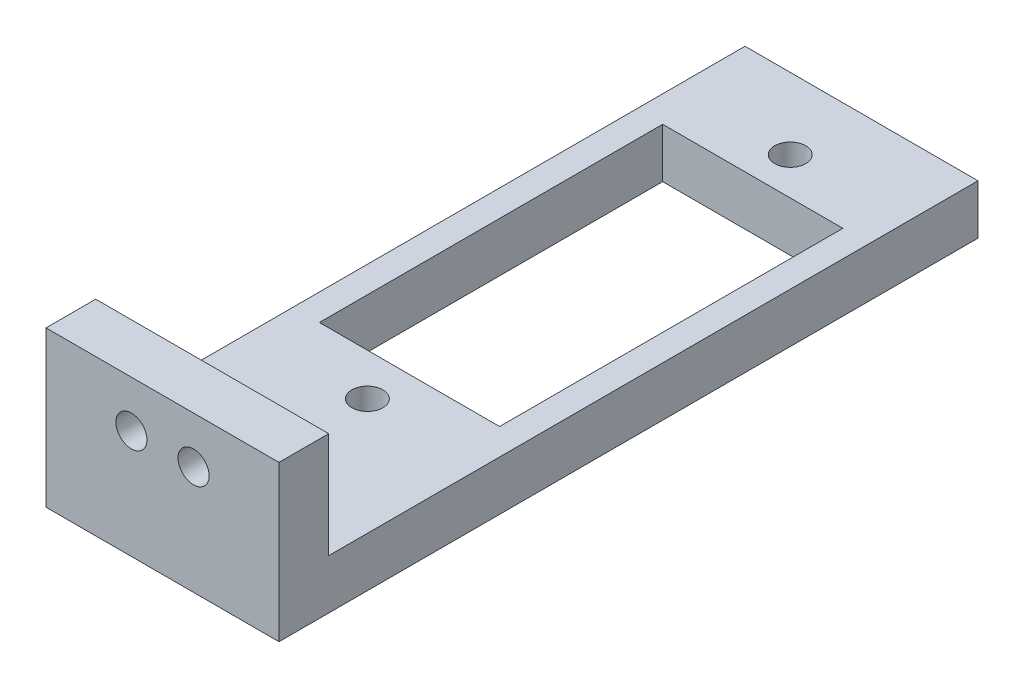
SolidWorks part; units mm, degrees
ref_plane "Front Plane" through (0, 0, 0) normal (0, 0, 1) x (1, 0, 0)
ref_plane "Top Plane" through (0, 0, 0) normal (0, 1, 0) x (1, 0, 0)
ref_plane "Right Plane" through (0, 0, 0) normal (1, 0, 0) x (0, 0, -1)
sketch "Sketch1" plane through (0, 0, 0) normal (0, 1, 0) x (1, 0, 0)
  line L1 (-7.5, 22.5) -> (7.5, 22.5)
  line L2 (-7.5, 22.5) -> (-7.5, -22.5)
  line L3 (-7.5, -22.5) -> (7.5, -22.5)
  line L4 (7.5, 22.5) -> (7.5, -22.5)
  line L5 (-7.5, 22.5) -> (7.5, -22.5) construction
  line L6 (-7.5, -22.5) -> (7.5, 22.5) construction
  point P0 (0, 0)
  dimension "D1" = 15
  dimension "D2" = 45
extrude "Boss-Extrude1" add sketch "Sketch1" along normal blind 10
sketch "Sketch4" plane through (0, 0, -22.5) normal (0, 0, -1) x (-1, 0, 0)
  line L0 (-7.5, 10) -> (-7.5, 0) construction
  line L1 (-7.5, 3.2) -> (7.5, 3.2)
  line L2 (-7.5, 3.2) -> (-7.5, 10)
  line L3 (-7.5, 10) -> (7.5, 10)
  line L4 (7.5, 3.2) -> (7.5, 10)
  dimension "D1" = 6.8
extrude "Cut-Extrude2" cut sketch "Sketch4" against normal blind 41.8
sketch "Sketch5" plane through (0, 0, 22.5) normal (0, 0, 1) x (1, 0, 0)
  line L1 (-7.5, 10) -> (7.5, 10) construction
  line L3 (-7.5, 10) -> (-7.5, 0) construction
  circle A0 centre (-2, 7) radius 1
  circle A1 centre (2, 7) radius 1
  dimension "D1" = 2
  dimension "D2" = 2
  dimension "D3" = 3
  dimension "D4" = 0
  dimension "D5" = 4
  dimension "D6" = 5.5
extrude "Cut-Extrude3" cut sketch "Sketch5" against normal through all
sketch "Sketch6" plane through (0, 3.2, 0) normal (0, 1, 0) x (1, 0, 0)
  line L1 (5.8, 15.5) -> (-5.8, 15.5)
  line L2 (5.8, 15.5) -> (5.8, -6.6)
  line L3 (5.8, -6.6) -> (-5.8, -6.6)
  line L4 (-5.8, 15.5) -> (-5.8, -6.6)
  line L5 (5.8, 15.5) -> (-5.8, -6.6) construction
  line L6 (5.8, -6.6) -> (-5.8, 15.5) construction
  line L9 (7.5, -19.3) -> (7.5, 22.5) construction
  line L11 (7.5, 22.5) -> (-7.5, 22.5) construction
  circle A0 centre (0, -9.31) radius 1
  circle A1 centre (0, 17.91) radius 1
  dimension "D5" = 2
  dimension "D6" = 2
  dimension "D7" = 2.71
  dimension "D8" = 2.41
  dimension "D1" = 11.6
  dimension "D2" = 22.1
  dimension "D3" = 1.7
  dimension "D4" = 7
extrude "Cut-Extrude4" cut sketch "Sketch6" against normal through all
